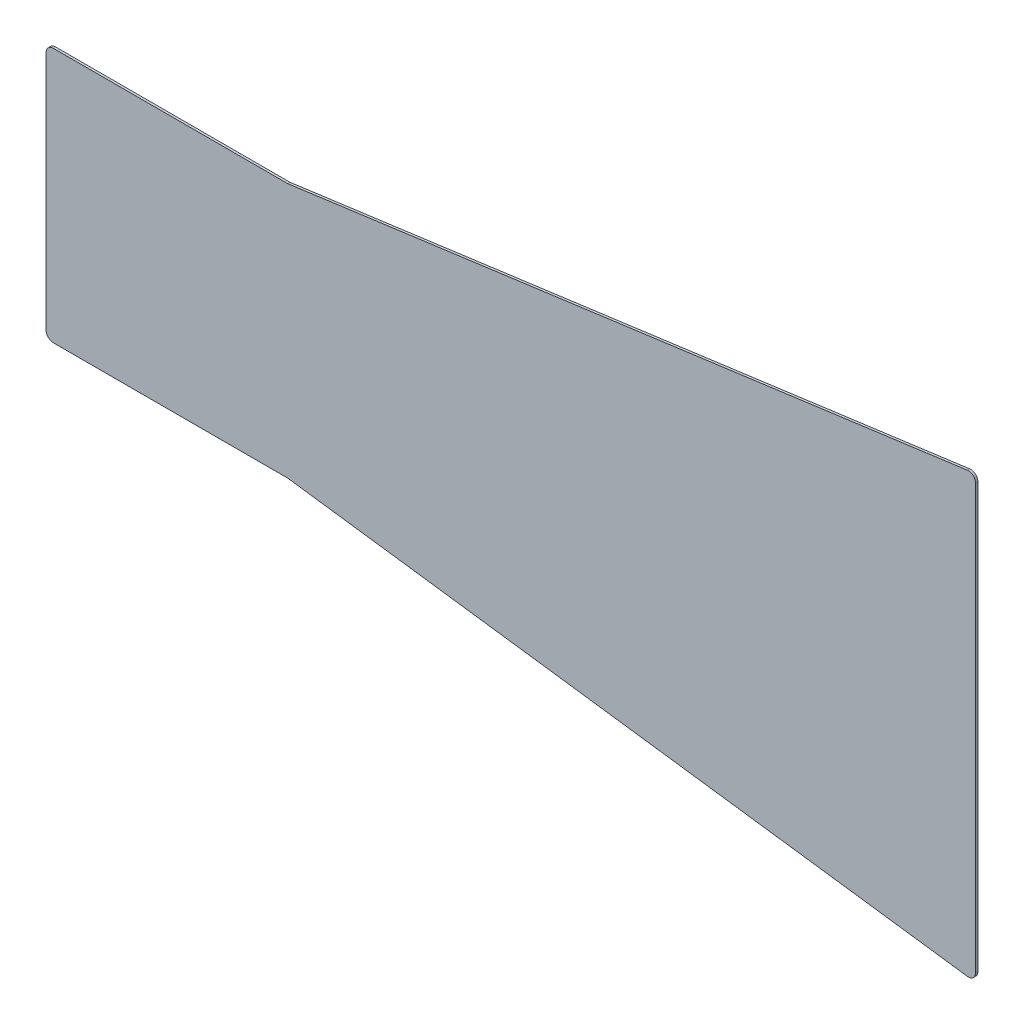
SolidWorks part; units mm, degrees
ref_plane "Front Plane" through (0, 0, 0) normal (0, 0, 1) x (1, 0, 0)
ref_plane "Top Plane" through (0, 0, 0) normal (0, 1, 0) x (1, 0, 0)
ref_plane "Right Plane" through (0, 0, 0) normal (1, 0, 0) x (0, 0, -1)
sketch "Sketch2" plane through (0, 0, 0) normal (0, 0, 1) x (1, 0, 0)
  line L0 (-1276.3617, -175.1092) -> (-1276.3617, 175.1092)
  line L2 (-1276.3617, 175.1092) -> (-944.7839, 175.1092)
  line L5 (-1276.3617, -175.1092) -> (-944.7839, -175.1092)
  line L6 (-944.7839, 175.1092) -> (0, 302.5295)
  line L7 (-944.7839, -175.1092) -> (0, -302.5295)
  line L9 (0, 302.5295) -> (0, -302.5295)
  point P12 (-944.7839, 0)
  dimension "D1" = 944.7839
  dimension "D2" = 1276.3617
  dimension "D3" = 175.1092
  dimension "D4" = 302.5295
  dimension "D5" = 175.1092
base flange "Base-Flange1" sketch "Sketch2" thickness 3.175 reverse thickness direction no parameters "D1"=0.7366
fillet "Fillet1" radius 10 5 edges at (0, 302.5295, -1.5875) (0, -302.5295, -1.5875) (-944.7839, -175.1092, -1.5875) (-1276.3617, -175.1092, -1.5875) (-1276.3617, 175.1092, -1.5875)
sketch "Bend-Lines1" [suppressed] plane through (0, 0, 0) normal (0, 1, 0) x (1, 0, 0)
sketch "Bounding-Box1" [suppressed] plane through (0, 0, 0) normal (0, 1, 0) x (1, 0, 0)
sheet metal parameters "Sheet-Metal1" thickness 3.175 parameters "D1"=0.7366
flat pattern "Flat-Pattern1" [suppressed]
sketch "Bend-Lines2" plane through (0, 0, 0) normal (0, 1, 0) x (1, 0, 0)
sketch3d "Bounding-Box2" [suppressed]
  line L0 (-1276.3617, 301.0903, 0) -> (0, 301.0903, 0) construction
  line L1 (-1276.3617, -301.0902, 0) -> (0, -301.0902, 0) construction
  line L2 (-1276.3617, 301.0903, 0) -> (-1276.3617, -301.0902, 0) construction
  line L3 (0, 301.0903, 0) -> (0, -301.0902, 0) construction
